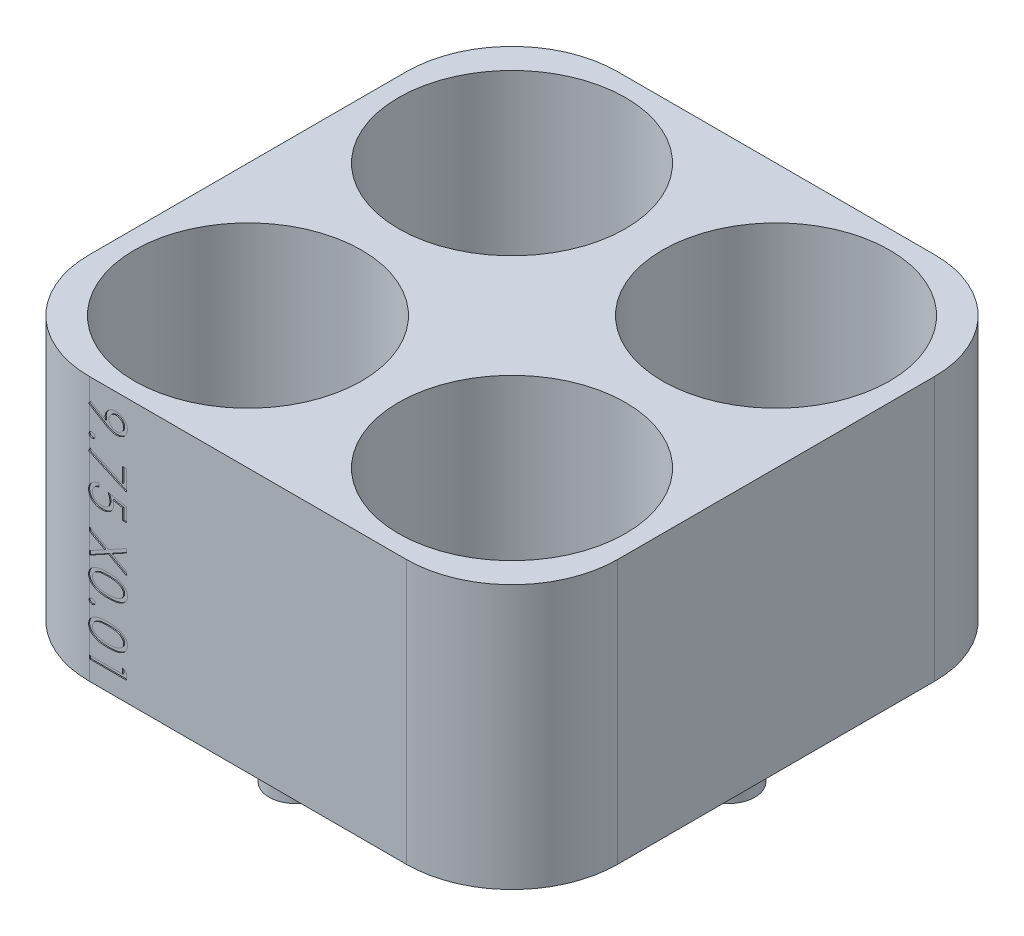
SolidWorks part; units mm, degrees
ref_plane "Alzado" through (0, 0, 0) normal (0, 0, 1) x (1, 0, 0)
ref_plane "Planta" through (0, 0, 0) normal (0, 1, 0) x (1, 0, 0)
ref_plane "Vista lateral" through (0, 0, 0) normal (1, 0, 0) x (0, 0, -1)
sketch "Croquis1" plane through (0, 0, 0) normal (0, 1, 0) x (1, 0, 0)
  line L1 (-25, 25) -> (25, 25)
  line L2 (-25, 25) -> (-25, -25)
  line L3 (-25, -25) -> (25, -25)
  line L4 (25, 25) -> (25, -25)
  line L5 (-25, 25) -> (25, -25) construction
  line L6 (-25, -25) -> (25, 25) construction
  point P0 (0, 0)
  dimension "D1" = 50
  dimension "D2" = 50
extrude "Saliente-Extruir1" add sketch "Croquis1" along normal blind 25
sketch "Croquis2" plane through (0, 25, 0) normal (0, 1, 0) x (1, 0, 0)
  line L1 (-25, 25) -> (-25, -25) construction
  line L2 (25, 25) -> (-25, 25) construction
  circle A0 centre (-12.5, 12.5) radius 10.75
  dimension "D1" = 21.5
  dimension "D2" = 12.5
  dimension "D3" = 12.5
extrude "Cortar-Extruir1" cut sketch "Croquis2" against normal blind 34
pattern_linear "MatrizL1" count 2 spacing 25 along (1, 0, 0) count 2 spacing 25 along (0, 0, 1) of "Cortar-Extruir1"
sketch "Croquis3" plane through (0, 0, 0) normal (0, -1, 0) x (1, 0, 0)
  line L0 (0, 7.2028) -> (0, 11.424) construction
  line L1 (-2.5, 0) -> (-5.3602, 0) construction
  circle A0 centre (0, 0) radius 2.5
  circle A1 centre (20.5, 0) radius 2.5
  circle A2 centre (-20.5, 0) radius 2.5
  circle A3 centre (0, 20.5) radius 2.5
  circle A4 centre (0, -20.5) radius 2.5
  dimension "D1" = 5
  dimension "D2" = 5
  dimension "D5" = 5
  dimension "D3" = 20.5
  dimension "D4" = 20.5
extrude "Saliente-Extruir2" add sketch "Croquis3" along normal blind 3
fillet "Redondeo3" radius 10 4 edges at (-25, 12.5, -25) (25, 12.5, -25) (25, 12.5, 25) (-25, 12.5, 25)
sketch "Croquis6" plane through (25, 0, 0) normal (1, 0, 0) x (0, 0, -1)
  line L5 (-15, 25) -> (15, 25) construction
  line L6 (-1.0144, 25) -> (5.0005, 25)
  line L7 (-1.0144, 25) -> (-1.0144, 23.8299)
  line L8 (-1.0144, 23.8299) -> (5.0005, 23.8299)
  line L9 (5.0005, 25) -> (5.0005, 23.8299)
sketch "Croquis7" plane through (0, 0, -25) normal (0, 0, -1) x (-1, 0, 0)
  line L0 (7.8632, 14.1683) -> (8.4844, 13.6947)
  line L1 (8.4844, 13.6947) -> (9.1494, 13.7051)
  line L2 (10.3053, 7.9462) -> (10.3053, 7.1749)
  line L3 (10.3053, 7.1749) -> (10.031, 7.1749)
  line L4 (10.031, 7.1749) -> (9.7567, 7.1749)
  line L5 (9.7567, 7.1749) -> (9.7567, 7.9064)
  line L6 (8.8152, 8.9851) -> (8.2479, 8.958)
  line L7 (8.2479, 8.958) -> (8.2217, 8.0664)
  line L8 (8.2217, 8.0664) -> (8.1956, 7.1749)
  line L9 (8.1956, 7.1749) -> (7.9246, 7.1749)
  line L10 (7.9246, 7.1749) -> (7.6536, 7.1749)
  line L11 (7.6536, 7.1749) -> (7.6536, 8.2734)
  line L12 (7.6536, 8.2734) -> (7.6536, 9.372)
  line L13 (7.6536, 9.372) -> (7.3564, 9.6424)
  line L14 (-2.7058, 14.0872) -> (-2.3467, 13.6793)
  line L15 (-2.3467, 13.6793) -> (-1.6645, 14.3361)
  line L16 (-1.6495, 11.3447) -> (-2.312, 11.9941)
  line L17 (-2.312, 11.9941) -> (-2.981, 11.3447)
  line L18 (-9.4499, 8.7294) -> (-8.8056, 8.7294)
  line L19 (-8.8056, 8.7294) -> (-8.8056, 8.455)
  line L20 (-8.8056, 8.455) -> (-8.8056, 8.1807)
  line L21 (-8.8056, 8.1807) -> (-9.4064, 8.1807)
  line L22 (-9.2629, 7.7692) -> (-8.577, 7.7692)
  line L23 (-8.577, 7.7692) -> (-8.577, 8.3636)
  line L24 (-8.577, 8.3636) -> (-8.577, 8.958)
  line L25 (-8.577, 8.958) -> (-9.2857, 8.9847)
  line L26 (-9.2857, 8.9847) -> (-9.9944, 9.0114)
  line L27 (-9.9944, 9.0114) -> (-9.9944, 9.2818)
  line L28 (-9.9944, 9.2818) -> (-9.9944, 9.5523)
  line L29 (-9.9944, 9.5523) -> (-9.304, 9.5523)
  line L30 (-5.4224, 9.2818) -> (-5.4224, 9.0114)
  line L31 (-5.4224, 9.0114) -> (-6.131, 8.9847)
  line L32 (-6.131, 8.9847) -> (-6.8397, 8.958)
  line L33 (-6.8397, 8.958) -> (-6.8659, 8.0664)
  line L34 (-6.8659, 8.0664) -> (-6.892, 7.1749)
  line L35 (-6.892, 7.1749) -> (-7.163, 7.1749)
  line L36 (-7.163, 7.1749) -> (-7.434, 7.1749)
  line L37 (-7.434, 7.1749) -> (-7.434, 8.1741)
  line L38 (-6.1873, 9.5523) -> (-5.4224, 9.5523)
  line L39 (-5.4224, 9.5523) -> (-5.4224, 9.2818)
  line L40 (-2.9535, 9.278) -> (-2.9535, 9.0037)
  line L41 (-2.9535, 9.0037) -> (-3.621, 9.0037)
  line L42 (-4.508, 7.9796) -> (-4.508, 7.1749)
  line L43 (-4.508, 7.1749) -> (-4.7906, 7.1749)
  line L44 (-4.7906, 7.1749) -> (-5.0732, 7.1749)
  line L45 (-5.0732, 7.1749) -> (-5.0421, 8.1431)
  line L46 (-3.7256, 9.5523) -> (-2.9535, 9.5523)
  line L47 (-2.9535, 9.5523) -> (-2.9535, 9.278)
  line L48 (-1.1662, 7.9978) -> (-1.8562, 7.9978)
  line L49 (-1.8562, 7.9978) -> (-1.8562, 8.2722)
  line L50 (-1.8562, 8.2722) -> (-1.8562, 8.5465)
  line L51 (-1.8562, 8.5465) -> (-1.2098, 8.5465)
  line L52 (-1.3075, 8.958) -> (-1.9934, 8.958)
  line L53 (-1.9934, 8.958) -> (-1.9934, 8.3636)
  line L54 (-1.9934, 8.3636) -> (-1.9934, 7.7692)
  line L55 (-1.9934, 7.7692) -> (-1.3761, 7.7422)
  line L56 (-1.3761, 7.7422) -> (-0.7589, 7.7152)
  line L57 (-0.7589, 7.7152) -> (-0.7589, 7.4353)
  line L58 (-0.7589, 7.4353) -> (-0.7589, 7.1555)
  line L59 (-0.7589, 7.1555) -> (-1.4994, 7.1891)
  line L60 (2.4415, 9.2818) -> (2.4415, 9.0114)
  line L61 (2.4415, 9.0114) -> (1.7328, 8.9847)
  line L62 (1.7328, 8.9847) -> (1.0242, 8.958)
  line L63 (1.0242, 8.958) -> (0.998, 8.0664)
  line L64 (0.998, 8.0664) -> (0.9718, 7.1749)
  line L65 (0.9718, 7.1749) -> (0.7008, 7.1749)
  line L66 (0.7008, 7.1749) -> (0.4298, 7.1749)
  line L67 (0.4298, 7.1749) -> (0.4298, 8.1741)
  line L68 (1.6766, 9.5523) -> (2.4415, 9.5523)
  line L69 (2.4415, 9.5523) -> (2.4415, 9.2818)
  line L70 (3.6718, 8.7294) -> (4.3617, 8.7294)
  line L71 (4.3617, 8.7294) -> (4.3617, 8.455)
  line L72 (4.3617, 8.455) -> (4.3617, 8.1807)
  line L73 (4.3617, 8.1807) -> (3.7153, 8.1807)
  line L74 (3.7641, 9.0037) -> (3.0816, 9.0037)
  line L75 (3.0816, 9.0037) -> (3.0816, 9.278)
  line L76 (3.0816, 9.278) -> (3.0816, 9.5523)
  line L77 (3.0816, 9.5523) -> (3.863, 9.5523)
  line L78 (7.1049, 8.3636) -> (7.1049, 7.1749)
  line L79 (7.1049, 7.1749) -> (6.8306, 7.1749)
  line L80 (6.8306, 7.1749) -> (6.5563, 7.1749)
  line L81 (6.5563, 7.1749) -> (6.5563, 8.3636)
  line L82 (6.5563, 8.3636) -> (6.5563, 9.5523)
  line L83 (6.5563, 9.5523) -> (6.8306, 9.5523)
  line L84 (6.8306, 9.5523) -> (7.1049, 9.5523)
  line L85 (7.1049, 9.5523) -> (7.1049, 8.3636)
  line L86 (0.8827, 14.6336) -> (0.7629, 14.6662)
  line L87 (-13.4691, 8.7327) -> (-13.4691, 7.7235)
  line L88 (-13.4691, 7.7235) -> (-12.4632, 7.7235)
  line L89 (-12.4632, 7.7235) -> (-11.4574, 7.7235)
  line L90 (-11.4574, 7.7235) -> (-11.4574, 7.9795)
  line L91 (-12.4358, 8.455) -> (-13.1948, 8.455)
  line L92 (-13.1948, 8.455) -> (-13.1948, 8.719)
  line L93 (-12.5776, 9.7156) -> (-13.4691, 9.7418)
  line L94 (-13.4691, 9.7418) -> (-13.4691, 8.7327)
  arc A0 (7.8207, 15.7172) -> (7.8364, 15.7705) centre (7.7385, 15.7705) ccw
  arc A1 (7.7403, 15.5996) -> (7.8207, 15.7172) centre (5.4553, 17.249) ccw
  arc A2 (7.6344, 15.4624) -> (7.7403, 15.5996) centre (5.511, 17.2088) ccw
  arc A3 (7.509, 15.3169) -> (7.6344, 15.4624) centre (4.4381, 18.0912) ccw
  arc A4 (7.509, 15.3169) -> (7.3859, 15.1667) centre (9.0083, 13.9623) ccw
  arc A5 (7.3859, 15.1667) -> (7.2866, 15.015) centre (8.617, 14.2528) ccw
  arc A6 (7.2866, 15.015) -> (7.2205, 14.8813) centre (8.3511, 14.4051) ccw
  arc A7 (7.2205, 14.8813) -> (7.2118, 14.7982) centre (7.3529, 14.8255) ccw
  arc A8 (7.2118, 14.7982) -> (7.2549, 14.7131) centre (7.3828, 14.8313) ccw
  arc A9 (7.2549, 14.7131) -> (7.4157, 14.5487) centre (10.2671, 17.4976) ccw
  arc A10 (7.4157, 14.5487) -> (7.6231, 14.3611) centre (10.3207, 17.5531) ccw
  arc A11 (7.6231, 14.3611) -> (7.8632, 14.1683) centre (11.5806, 19.0439) ccw
  arc A12 (9.1494, 13.7051) -> (9.6224, 13.7371) centre (9.0782, 18.267) ccw
  arc A13 (9.6224, 13.7371) -> (9.942, 13.8238) centre (9.4861, 14.8713) ccw
  arc A14 (9.942, 13.8238) -> (10.2456, 14.0053) centre (9.39, 15.0921) ccw
  arc A15 (10.2456, 14.0053) -> (10.6786, 14.3706) centre (5.0774, 20.5705) ccw
  arc A16 (10.6786, 14.3706) -> (10.8157, 14.5072) centre (9.344, 15.8478) ccw
  arc A17 (10.8157, 14.5072) -> (10.9316, 14.6498) centre (9.6175, 15.5987) ccw
  arc A18 (10.9316, 14.6498) -> (11.0142, 14.7795) centre (9.864, 15.4207) ccw
  arc A19 (11.0142, 14.7795) -> (11.0368, 14.8667) centre (10.8577, 14.8667) ccw
  arc A20 (11.0368, 14.8667) -> (11.0138, 14.9543) centre (10.8588, 14.8667) ccw
  arc A21 (11.0138, 14.9543) -> (10.9294, 15.0856) centre (9.8293, 14.2855) ccw
  arc A22 (10.9294, 15.0856) -> (10.8111, 15.2305) centre (9.5779, 14.1027) ccw
  arc A23 (10.8111, 15.2305) -> (10.6711, 15.3696) centre (9.282, 13.8321) ccw
  arc A24 (10.531, 15.5023) -> (10.6711, 15.3696) centre (13.4494, 18.4448) ccw
  arc A25 (10.4128, 15.6274) -> (10.531, 15.5023) centre (12.3843, 17.371) ccw
  arc A26 (10.3221, 15.7353) -> (10.4128, 15.6274) centre (12.5085, 17.4808) ccw
  arc A27 (10.3053, 15.7832) -> (10.3221, 15.7353) centre (10.3821, 15.7832) ccw
  arc A28 (10.3608, 15.8219) -> (10.3053, 15.7832) centre (10.3466, 15.7832) ccw
  arc A29 (10.5656, 15.7289) -> (10.3608, 15.8219) centre (9.8279, 14.3762) ccw
  arc A30 (10.8002, 15.5792) -> (10.5656, 15.7289) centre (9.599, 13.9564) ccw
  arc A31 (10.9826, 15.4138) -> (10.8002, 15.5792) centre (10.0591, 14.578) ccw
  arc A32 (10.9826, 15.4138) -> (11.0637, 15.3403) centre (11.3967, 15.7885) ccw
  arc A33 (11.0637, 15.3403) -> (11.1631, 15.2781) centre (11.5017, 15.9299) ccw
  arc A34 (11.1631, 15.2781) -> (11.265, 15.2354) centre (11.4705, 15.8698) ccw
  arc A35 (11.265, 15.2354) -> (11.3528, 15.2216) centre (11.3528, 15.5063) ccw
  arc A36 (11.5105, 15.1947) -> (11.3528, 15.2216) centre (11.3528, 14.7446) ccw
  arc A37 (11.6455, 15.1174) -> (11.5105, 15.1947) centre (11.3692, 14.7916) ccw
  arc A38 (11.7362, 15.0028) -> (11.6455, 15.1174) centre (11.405, 14.8338) ccw
  arc A39 (11.7684, 14.8692) -> (11.7362, 15.0028) centre (11.4744, 14.8692) ccw
  arc A40 (11.7684, 14.8692) -> (11.79, 14.7971) centre (11.8993, 14.8692) ccw
  arc A41 (11.79, 14.7971) -> (11.8825, 14.6685) centre (13.4278, 15.8772) ccw
  arc A42 (11.8825, 14.6685) -> (12.0082, 14.5215) centre (13.633, 16.0377) ccw
  arc A43 (12.0082, 14.5215) -> (12.157, 14.3724) centre (14.2933, 16.654) ccw
  arc A44 (12.438, 14.0823) -> (12.157, 14.3724) centre (9.3325, 11.356) ccw
  arc A45 (12.4278, 13.9645) -> (12.438, 14.0823) centre (12.3765, 14.0283) ccw
  arc A46 (12.2881, 13.9582) -> (12.4278, 13.9645) centre (12.3537, 14.0566) ccw
  arc A47 (11.9498, 14.2059) -> (12.2881, 13.9582) centre (14.8744, 17.8451) ccw
  arc A48 (11.9498, 14.2059) -> (11.8015, 14.3147) centre (10.6506, 12.5892) ccw
  arc A49 (11.8015, 14.3147) -> (11.6481, 14.4066) centre (10.7739, 12.7741) ccw
  arc A50 (11.6481, 14.4066) -> (11.5101, 14.4719) centre (10.9149, 13.0372) ccw
  arc A51 (11.5101, 14.4719) -> (11.4191, 14.4901) centre (11.4191, 14.2524) ccw
  arc A52 (11.4191, 14.4901) -> (11.2737, 14.4365) centre (11.4191, 14.2662) ccw
  arc A53 (11.2737, 14.4365) -> (11.0199, 14.2002) centre (13.8839, 11.378) ccw
  arc A54 (11.0199, 14.2002) -> (10.703, 13.8512) centre (15.1341, 10.1459) ccw
  arc A55 (10.703, 13.8512) -> (10.3171, 13.3718) centre (23.3414, 3.2831) ccw
  arc A56 (10.3171, 13.3718) -> (10.2657, 13.2677) centre (10.5478, 13.1931) ccw
  arc A57 (10.2657, 13.2677) -> (10.2276, 13.0849) centre (11.9738, 12.816) ccw
  arc A58 (10.2276, 13.0849) -> (10.2027, 12.8512) centre (12.7023, 12.7038) ccw
  arc A59 (10.2027, 12.8512) -> (10.1946, 12.5765) centre (14.86, 12.5765) ccw
  arc A60 (10.1946, 12.5765) -> (10.204, 12.2376) centre (16.3162, 12.5765) ccw
  arc A61 (10.204, 12.2376) -> (10.2357, 12.0059) centre (11.6523, 12.3179) ccw
  arc A62 (10.2357, 12.0059) -> (10.2978, 11.8205) centre (11.1359, 12.2042) ccw
  arc A63 (10.2978, 11.8205) -> (10.4015, 11.6373) centre (11.4166, 12.3327) ccw
  arc A64 (10.4015, 11.6373) -> (10.6632, 11.2924) centre (14.0932, 14.1663) ccw
  arc A65 (10.6632, 11.2924) -> (10.9626, 10.9662) centre (14.4096, 14.4314) ccw
  arc A66 (10.9626, 10.9662) -> (11.2451, 10.7049) centre (14.694, 14.7173) ccw
  arc A67 (11.2451, 10.7049) -> (11.3944, 10.6496) centre (11.3944, 10.8787) ccw
  arc A68 (11.3944, 10.6496) -> (11.4678, 10.669) centre (11.3944, 10.7979) ccw
  arc A69 (11.4678, 10.669) -> (11.591, 10.7467) centre (10.6583, 12.0903) ccw
  arc A70 (11.591, 10.7467) -> (11.7308, 10.8535) centre (10.4984, 12.3206) ccw
  arc A71 (11.7308, 10.8535) -> (11.8705, 10.98) centre (10.1105, 12.7824) ccw
  arc A72 (12.1865, 11.2633) -> (11.8705, 10.98) centre (15.333, 7.434) ccw
  arc A73 (12.3254, 11.2717) -> (12.1865, 11.2633) centre (12.2618, 11.1718) ccw
  arc A74 (12.3462, 11.1583) -> (12.3254, 11.2717) centre (12.2831, 11.2053) ccw
  arc A75 (12.0866, 10.8425) -> (12.3462, 11.1583) centre (8.8334, 13.7815) ccw
  arc A76 (12.0866, 10.8425) -> (11.9503, 10.6793) centre (14.1042, 9.0197) ccw
  arc A77 (11.9503, 10.6793) -> (11.8331, 10.5124) centre (13.7779, 9.2711) ccw
  arc A78 (11.8331, 10.5124) -> (11.7469, 10.3632) centre (13.4831, 9.4593) ccw
  arc A79 (11.7469, 10.3632) -> (11.7198, 10.2678) centre (11.9646, 10.2498) ccw
  arc A80 (11.6821, 10.1339) -> (11.7198, 10.2678) centre (11.3722, 10.2934) ccw
  arc A81 (11.5944, 10.0217) -> (11.6821, 10.1339) centre (11.3432, 10.3083) ccw
  arc A82 (11.4687, 9.9467) -> (11.5944, 10.0217) centre (11.3273, 10.3265) ccw
  arc A83 (11.3222, 9.9195) -> (11.4687, 9.9467) centre (11.3174, 10.353) ccw
  arc A84 (11.3222, 9.9195) -> (11.2525, 9.9004) centre (11.3238, 9.7769) ccw
  arc A85 (11.2525, 9.9004) -> (11.124, 9.8199) centre (12.3164, 8.0596) ccw
  arc A86 (11.124, 9.8199) -> (10.9761, 9.711) centre (12.4479, 7.8656) ccw
  arc A87 (10.9761, 9.711) -> (10.8246, 9.5823) centre (12.9922, 7.183) ccw
  arc A88 (10.5215, 9.3355) -> (10.8246, 9.5823) centre (8.2644, 12.4162) ccw
  arc A89 (10.4143, 9.3612) -> (10.5215, 9.3355) centre (10.4788, 9.3938) ccw
  arc A90 (10.43, 9.5064) -> (10.4143, 9.3612) centre (10.534, 9.4217) ccw
  arc A91 (10.7064, 9.816) -> (10.43, 9.5064) centre (14.0228, 6.5776) ccw
  arc A92 (10.7064, 9.816) -> (10.8329, 9.9529) centre (8.2825, 12.1828) ccw
  arc A93 (10.8329, 9.9529) -> (10.9398, 10.0845) centre (9.0895, 11.4772) ccw
  arc A94 (10.9398, 10.0845) -> (11.0198, 10.1981) centre (9.1777, 11.4109) ccw
  arc A95 (11.0198, 10.1981) -> (11.0368, 10.255) centre (10.9335, 10.255) ccw
  arc A96 (11.0368, 10.255) -> (10.9841, 10.3809) centre (10.86, 10.255) ccw
  arc A97 (10.9841, 10.3809) -> (10.491, 10.8589) centre (-17.2866, -18.295) ccw
  arc A98 (10.491, 10.8589) -> (9.9956, 11.3213) centre (-12.443, -13.2114) ccw
  arc A99 (9.9956, 11.3213) -> (9.8429, 11.3925) centre (9.806, 11.1141) ccw
  arc A100 (9.8429, 11.3925) -> (9.4672, 11.4208) centre (9.4061, 8.0975) ccw
  arc A101 (9.4672, 11.4208) -> (8.9452, 11.4189) centre (9.2489, -0.4536) ccw
  arc A102 (8.9452, 11.4189) -> (8.4316, 11.3984) centre (9.4014, -6.4151) ccw
  arc A103 (8.4316, 11.3984) -> (8.2536, 11.3519) centre (8.4566, 10.9386) ccw
  arc A104 (8.2536, 11.3519) -> (7.9869, 11.175) centre (8.8016, 10.2362) ccw
  arc A105 (7.9869, 11.175) -> (7.6125, 10.8268) centre (12.8611, 5.5589) ccw
  arc A106 (7.6125, 10.8268) -> (7.2577, 10.4565) centre (15.4297, 2.9809) ccw
  arc A107 (7.2577, 10.4565) -> (7.1964, 10.2985) centre (7.4305, 10.2985) ccw
  arc A108 (7.1964, 10.2985) -> (7.2145, 10.2244) centre (7.3572, 10.2985) ccw
  arc A109 (7.2145, 10.2244) -> (7.2822, 10.1089) centre (8.3772, 10.8285) ccw
  arc A110 (7.2822, 10.1089) -> (7.3767, 9.9798) centre (8.6008, 10.9755) ccw
  arc A111 (7.3767, 9.9798) -> (7.4886, 9.8538) centre (8.8808, 11.2032) ccw
  arc A112 (7.4886, 9.8538) -> (7.6904, 9.6721) centre (8.9275, 11.2485) ccw
  arc A113 (7.6904, 9.6721) -> (7.8549, 9.5907) centre (7.9674, 10.025) ccw
  arc A114 (7.8549, 9.5907) -> (8.0864, 9.5585) centre (8.1095, 10.5738) ccw
  arc A115 (8.0864, 9.5585) -> (8.6545, 9.552) centre (8.6644, 35.0044) ccw
  arc A116 (9.1215, 9.544) -> (8.6545, 9.552) centre (8.649, -4.5201) ccw
  arc A117 (9.4164, 9.5162) -> (9.1215, 9.544) centre (9.0393, 7.0978) ccw
  arc A118 (9.6332, 9.4615) -> (9.4164, 9.5162) centre (9.2303, 8.3229) ccw
  arc A119 (9.8275, 9.3691) -> (9.6332, 9.4615) centre (9.2866, 8.4818) ccw
  arc A120 (10.07, 9.1656) -> (9.8275, 9.3691) centre (9.2785, 8.4685) ccw
  arc A121 (10.2136, 8.9165) -> (10.07, 9.1656) centre (9.5244, 8.685) ccw
  arc A122 (10.2855, 8.5518) -> (10.2136, 8.9165) centre (8.8473, 8.4577) ccw
  arc A123 (10.3053, 7.9462) -> (10.2855, 8.5518) centre (1.0313, 7.9462) ccw
  arc A124 (9.7567, 7.9064) -> (9.7228, 8.5244) centre (4.1088, 7.9064) ccw
  arc A125 (9.7228, 8.5244) -> (9.5911, 8.8245) centre (9.1787, 8.4645) ccw
  arc A126 (9.5911, 8.8245) -> (9.3262, 8.9654) centre (9.2738, 8.5476) ccw
  arc A127 (9.3262, 8.9654) -> (8.8152, 8.9851) centre (8.9569, 6.0198) ccw
  arc A128 (7.3564, 9.6424) -> (7.2288, 9.746) centre (6.3626, 8.55) ccw
  arc A129 (7.2288, 9.746) -> (7.0914, 9.8341) centre (6.3868, 8.5834) ccw
  arc A130 (7.0914, 9.8341) -> (6.9639, 9.8963) centre (6.5037, 8.7908) ccw
  arc A131 (6.9639, 9.8963) -> (6.8717, 9.9154) centre (6.8682, 9.6665) ccw
  arc A132 (6.7131, 9.9457) -> (6.8717, 9.9154) centre (6.8784, 10.381) ccw
  arc A133 (6.5817, 10.028) -> (6.7131, 9.9457) centre (6.8541, 10.3171) ccw
  arc A134 (6.4953, 10.1513) -> (6.5817, 10.028) centre (6.8364, 10.2983) ccw
  arc A135 (6.4648, 10.2988) -> (6.4953, 10.1513) centre (6.8376, 10.2988) ccw
  arc A136 (6.4648, 10.2988) -> (6.4415, 10.3832) centre (6.3005, 10.2988) ccw
  arc A137 (6.4415, 10.3832) -> (6.3508, 10.5191) centre (5.0271, 9.5374) ccw
  arc A138 (6.3508, 10.5191) -> (6.2253, 10.6717) centre (4.7662, 9.3438) ccw
  arc A139 (6.2253, 10.6717) -> (6.0768, 10.8221) centre (4.3143, 8.9327) ccw
  arc A140 (5.9325, 10.9654) -> (6.0768, 10.8221) centre (8.2667, 13.1698) ccw
  arc A141 (5.8213, 11.0963) -> (5.9325, 10.9654) centre (7.1292, 12.0955) ccw
  arc A142 (5.7469, 11.2041) -> (5.8213, 11.0963) centre (6.8945, 11.9163) ccw
  arc A143 (5.7519, 11.2473) -> (5.7469, 11.2041) centre (5.7767, 11.2225) ccw
  arc A144 (5.8578, 11.2647) -> (5.7519, 11.2473) centre (5.8169, 11.1823) ccw
  arc A145 (6.131, 11.1127) -> (5.8578, 11.2647) centre (4.3782, 8.2823) ccw
  arc A146 (6.3917, 10.9301) -> (6.131, 11.1127) centre (4.6509, 8.7227) ccw
  arc A147 (6.4986, 10.7849) -> (6.3917, 10.9301) centre (6.1812, 10.6631) ccw
  arc A148 (6.4986, 10.7849) -> (6.6024, 10.6772) centre (6.6776, 10.8536) ccw
  arc A149 (6.6024, 10.6772) -> (6.7608, 10.6678) centre (6.6948, 10.8938) ccw
  arc A150 (6.7608, 10.6678) -> (6.9698, 10.7749) centre (6.5856, 11.2676) ccw
  arc A151 (6.9698, 10.7749) -> (7.2092, 10.9925) centre (5.6507, 12.4663) ccw
  arc A152 (7.2092, 10.9925) -> (7.6024, 11.44) centre (1.2864, 16.5932) ccw
  arc A153 (7.6024, 11.44) -> (7.8101, 11.7698) centre (6.3648, 12.4497) ccw
  arc A154 (7.8101, 11.7698) -> (7.9156, 12.1133) centre (6.658, 12.3118) ccw
  arc A155 (7.9156, 12.1133) -> (7.9614, 12.5915) centre (4.0276, 12.7269) ccw
  arc A156 (7.9614, 12.5915) -> (7.9658, 12.9697) centre (-0.2685, 12.8749) ccw
  arc A157 (7.9658, 12.9697) -> (7.9414, 13.1961) centre (6.7728, 12.9559) ccw
  arc A158 (7.9414, 13.1961) -> (7.8789, 13.3759) centre (7.2334, 13.0506) ccw
  arc A159 (7.8789, 13.3759) -> (7.7592, 13.5757) centre (6.4557, 12.6586) ccw
  arc A160 (7.7592, 13.5757) -> (7.479, 13.9431) centre (2.8327, 10.1098) ccw
  arc A161 (7.479, 13.9431) -> (7.2074, 14.235) centre (4.8934, 11.8099) ccw
  arc A162 (7.2074, 14.235) -> (6.9674, 14.4357) centre (5.5572, 12.5055) ccw
  arc A163 (6.9674, 14.4357) -> (6.8009, 14.4901) centre (6.8009, 14.2078) ccw
  arc A164 (6.8009, 14.4901) -> (6.7093, 14.4691) centre (6.8009, 14.2792) ccw
  arc A165 (6.7093, 14.4691) -> (6.5669, 14.3915) centre (7.4157, 13.0051) ccw
  arc A166 (6.5669, 14.3915) -> (6.4078, 14.2829) centre (7.5845, 12.7294) ccw
  arc A167 (6.4078, 14.2829) -> (6.2526, 14.1543) centre (7.8163, 12.4235) ccw
  arc A168 (5.9495, 13.9075) -> (6.2526, 14.1543) centre (3.6924, 16.9882) ccw
  arc A169 (5.8423, 13.9332) -> (5.9495, 13.9075) centre (5.9068, 13.9658) ccw
  arc A170 (5.858, 14.0784) -> (5.8423, 13.9332) centre (5.962, 13.9937) ccw
  arc A171 (6.1344, 14.388) -> (5.858, 14.0784) centre (9.4508, 11.1496) ccw
  arc A172 (6.1344, 14.388) -> (6.2609, 14.5277) centre (4.3353, 16.1447) ccw
  arc A173 (6.2609, 14.5277) -> (6.3678, 14.6675) centre (4.7953, 15.7585) ccw
  arc A174 (6.3678, 14.6675) -> (6.4454, 14.7907) centre (5.0259, 15.5984) ccw
  arc A175 (6.4454, 14.7907) -> (6.4648, 14.8643) centre (6.3162, 14.8643) ccw
  arc A176 (6.4958, 14.9979) -> (6.4648, 14.8643) centre (6.7686, 14.8643) ccw
  arc A177 (6.5836, 15.1144) -> (6.4958, 14.9979) centre (6.8417, 14.8285) ccw
  arc A178 (6.7126, 15.1939) -> (6.5836, 15.1144) centre (6.8641, 14.8037) ccw
  arc A179 (6.8607, 15.2216) -> (6.7126, 15.1939) centre (6.8607, 14.8125) ccw
  arc A180 (6.8607, 15.2216) -> (6.9513, 15.2418) centre (6.8607, 15.4347) ccw
  arc A181 (6.9513, 15.2418) -> (7.0893, 15.3156) centre (6.3077, 16.6115) ccw
  arc A182 (7.0893, 15.3156) -> (7.2427, 15.4191) centre (6.1486, 16.8752) ccw
  arc A183 (7.2427, 15.4191) -> (7.3913, 15.5416) centre (5.9615, 17.1242) ccw
  arc A184 (7.6394, 15.7605) -> (7.3913, 15.5416) centre (16.6562, 5.2864) ccw
  arc A185 (7.7547, 15.8381) -> (7.6394, 15.7605) centre (8.0247, 15.3129) ccw
  arc A186 (7.8098, 15.8308) -> (7.7547, 15.8381) centre (7.777, 15.7948) ccw
  arc A187 (7.8364, 15.7705) -> (7.8098, 15.8308) centre (7.7548, 15.7705) ccw
  arc A188 (-4.1735, 15.2369) -> (-4.6255, 15.4401) centre (-5.4338, 13.0378) ccw
  arc A189 (-3.6355, 14.8943) -> (-4.1735, 15.2369) centre (-7.5658, 9.3178) ccw
  arc A190 (-3.1136, 14.4889) -> (-3.6355, 14.8943) centre (-7.7378, 9.0737) ccw
  arc A191 (-2.7058, 14.0872) -> (-3.1136, 14.4889) centre (-5.7294, 11.4256) ccw
  arc A192 (-1.0017, 14.9126) -> (-1.6645, 14.3361) centre (4.3593, 8.0795) ccw
  arc A193 (-0.4217, 15.2765) -> (-1.0017, 14.9126) centre (1.0153, 12.3417) ccw
  arc A194 (0.1537, 15.4744) -> (-0.4217, 15.2765) centre (0.6598, 13.0678) ccw
  arc A195 (0.7956, 15.5407) -> (0.1537, 15.4744) centre (0.7915, 12.4417) ccw
  arc A196 (1.1847, 15.5292) -> (0.7956, 15.5407) centre (0.7865, 8.6665) ccw
  arc A197 (1.4476, 15.4913) -> (1.1847, 15.5292) centre (1.0942, 13.9692) ccw
  arc A198 (1.6838, 15.4122) -> (1.4476, 15.4913) centre (1.151, 14.2139) ccw
  arc A199 (1.9772, 15.2664) -> (1.6838, 15.4122) centre (0.1274, 11.9118) ccw
  arc A200 (2.3788, 14.9896) -> (1.9772, 15.2664) centre (0.7926, 13.1182) ccw
  arc A201 (2.763, 14.6116) -> (2.3788, 14.9896) centre (0.0248, 12.2123) ccw
  arc A202 (3.0797, 14.1901) -> (2.763, 14.6116) centre (0.1218, 12.2973) ccw
  arc A203 (3.2772, 13.7827) -> (3.0797, 14.1901) centre (1.4583, 13.1525) ccw
  arc A204 (3.3233, 13.6068) -> (3.2772, 13.7827) centre (2.1631, 13.3967) ccw
  arc A205 (3.3622, 13.3516) -> (3.3233, 13.6068) centre (-1.2114, 12.7856) ccw
  arc A206 (3.3893, 13.0687) -> (3.3622, 13.3516) centre (-1.7499, 12.7189) ccw
  arc A207 (3.399, 12.7984) -> (3.3893, 13.0687) centre (-0.8303, 12.7815) ccw
  arc A208 (3.3017, 12.0425) -> (3.399, 12.7984) centre (0.506, 12.7868) ccw
  arc A209 (3.0106, 11.3734) -> (3.3017, 12.0425) centre (0.9449, 12.67) ccw
  arc A210 (2.5277, 10.8085) -> (3.0106, 11.3734) centre (0.8575, 12.7249) ccw
  arc A211 (1.8674, 10.3584) -> (2.5277, 10.8085) centre (0.3078, 13.3556) ccw
  arc A212 (1.6445, 10.2614) -> (1.8674, 10.3584) centre (1.0576, 11.9146) ccw
  arc A213 (1.4171, 10.1997) -> (1.6445, 10.2614) centre (1.1262, 11.7213) ccw
  arc A214 (1.1489, 10.1657) -> (1.4171, 10.1997) centre (1.0129, 12.3142) ccw
  arc A215 (0.7956, 10.1535) -> (1.1489, 10.1657) centre (0.7595, 16.3192) ccw
  arc A216 (0.1493, 10.217) -> (0.7956, 10.1535) centre (0.7772, 13.2854) ccw
  arc A217 (-0.427, 10.4128) -> (0.1493, 10.217) centre (0.6358, 12.5941) ccw
  arc A218 (-1.0017, 10.7741) -> (-0.427, 10.4128) centre (0.9552, 13.2498) ccw
  arc A219 (-1.6495, 11.3447) -> (-1.0017, 10.7741) centre (4.0247, 17.1332) ccw
  arc A220 (-3.6326, 10.7749) -> (-2.981, 11.3447) centre (-8.7936, 17.3333) ccw
  arc A221 (-4.2072, 10.414) -> (-3.6326, 10.7749) centre (-5.6168, 13.2963) ccw
  arc A222 (-4.7806, 10.2172) -> (-4.2072, 10.414) centre (-5.2824, 12.6125) ccw
  arc A223 (-5.4224, 10.1507) -> (-4.7806, 10.2172) centre (-5.4216, 13.2772) ccw
  arc A224 (-5.9428, 10.1875) -> (-5.4224, 10.1507) centre (-5.4215, 13.8704) ccw
  arc A225 (-6.3703, 10.299) -> (-5.9428, 10.1875) centre (-5.6718, 12.1016) ccw
  arc A226 (-6.7684, 10.507) -> (-6.3703, 10.299) centre (-5.6435, 12.1747) ccw
  arc A227 (-7.1992, 10.8393) -> (-6.7684, 10.507) centre (-4.3734, 14.0577) ccw
  arc A228 (-7.628, 11.3675) -> (-7.1992, 10.8393) centre (-5.8601, 12.3645) ccw
  arc A229 (-7.93, 12.0833) -> (-7.628, 11.3675) centre (-4.6606, 13.0409) ccw
  arc A230 (-8.0632, 12.8536) -> (-7.93, 12.0833) centre (-4.6226, 13.052) ccw
  arc A231 (-7.9916, 13.5443) -> (-8.0632, 12.8536) centre (-5.8998, 12.9784) ccw
  arc A232 (-7.7267, 14.1527) -> (-7.9916, 13.5443) centre (-5.7966, 12.9505) ccw
  arc A233 (-7.2696, 14.7396) -> (-7.7267, 14.1527) centre (-4.7051, 12.2706) ccw
  arc A234 (-6.7051, 15.2141) -> (-7.2696, 14.7396) centre (-4.7436, 12.3076) ccw
  arc A235 (-6.1205, 15.4878) -> (-6.7051, 15.2141) centre (-5.5415, 13.4899) ccw
  arc A236 (-5.767, 15.558) -> (-6.1205, 15.4878) centre (-5.537, 13.4743) ccw
  arc A237 (-5.3825, 15.573) -> (-5.767, 15.558) centre (-5.469, 12.8582) ccw
  arc A238 (-4.9932, 15.5333) -> (-5.3825, 15.573) centre (-5.4718, 12.7708) ccw
  arc A239 (-4.6255, 15.4401) -> (-4.9932, 15.5333) centre (-5.4167, 13.0887) ccw
  arc A240 (-11.1477, 9.8357) -> (-11.2454, 9.9892) centre (-12.2316, 9.2535) ccw
  arc A241 (-11.1073, 9.7094) -> (-11.1477, 9.8357) centre (-11.4682, 9.6636) ccw
  arc A242 (-11.1098, 9.5586) -> (-11.1073, 9.7094) centre (-11.6324, 9.6428) ccw
  arc A243 (-11.1588, 9.3072) -> (-11.1098, 9.5586) centre (-14.9842, 10.1826) ccw
  arc A244 (-11.1588, 9.3072) -> (-11.2075, 9.0588) centre (-7.2141, 8.4045) ccw
  arc A245 (-11.2075, 9.0588) -> (-11.211, 8.9103) centre (-10.6769, 8.9718) ccw
  arc A246 (-11.211, 8.9103) -> (-11.1734, 8.79) centre (-10.877, 8.9488) ccw
  arc A247 (-11.1734, 8.79) -> (-11.0833, 8.6523) centre (-10.3418, 9.2356) ccw
  arc A248 (-10.9464, 8.3681) -> (-11.0833, 8.6523) centre (-11.6578, 8.2004) ccw
  arc A249 (-10.9027, 7.9815) -> (-10.9464, 8.3681) centre (-12.542, 7.992) ccw
  arc A250 (-10.9507, 7.6059) -> (-10.9027, 7.9815) centre (-12.4755, 7.9916) ccw
  arc A251 (-11.0916, 7.3578) -> (-10.9507, 7.6059) centre (-11.4715, 7.7376) ccw
  arc A252 (-11.2431, 7.2577) -> (-11.0916, 7.3578) centre (-11.4122, 7.6783) ccw
  arc A253 (-11.4485, 7.2044) -> (-11.2431, 7.2577) centre (-11.5527, 8.028) ccw
  arc A254 (-11.7931, 7.1802) -> (-11.4485, 7.2044) centre (-11.8372, 10.2753) ccw
  arc A255 (-12.5364, 7.1749) -> (-11.7931, 7.1802) centre (-12.5364, 59.3435) ccw
  arc A256 (-13.1097, 7.1811) -> (-12.5364, 7.1749) centre (-12.5364, 33.73) ccw
  arc A257 (-13.5165, 7.2017) -> (-13.1097, 7.1811) centre (-12.9587, 14.1743) ccw
  arc A258 (-13.8053, 7.2334) -> (-13.5165, 7.2017) centre (-13.1246, 12.1001) ccw
  arc A259 (-13.908, 7.2846) -> (-13.8053, 7.2334) centre (-13.7802, 7.4124) ccw
  arc A260 (-13.9922, 7.4804) -> (-13.908, 7.2846) centre (-13.7044, 7.4882) ccw
  arc A261 (-14.0195, 8.7564) -> (-13.9922, 7.4804) centre (98.3572, 10.5257) ccw
  arc A262 (-14.0326, 10.035) -> (-14.0195, 8.7564) centre (101.8739, 10.5812) ccw
  arc A263 (-13.9543, 10.2253) -> (-14.0326, 10.035) centre (-13.7652, 10.0362) ccw
  arc A264 (-13.8976, 10.2502) -> (-13.9543, 10.2253) centre (-13.8941, 10.1651) ccw
  arc A265 (-13.5482, 10.2627) -> (-13.8976, 10.2502) centre (-12.7256, -17.6614) ccw
  arc A266 (-13.1369, 10.2686) -> (-13.5482, 10.2627) centre (-13.1495, -3.2714) ccw
  arc A267 (-12.661, 10.2634) -> (-13.1369, 10.2686) centre (-13.1594, -13.9436) ccw
  arc A268 (-11.8561, 10.2422) -> (-12.661, 10.2634) centre (-14.0796, -58.6346) ccw
  arc A269 (-11.5649, 10.2095) -> (-11.8561, 10.2422) centre (-11.9156, 8.3994) ccw
  arc A270 (-11.3946, 10.1359) -> (-11.5649, 10.2095) centre (-11.647, 9.7854) ccw
  arc A271 (-11.2454, 9.9892) -> (-11.3946, 10.1359) centre (-11.7962, 9.5783) ccw
  arc A272 (-8.1526, 9.2758) -> (-8.355, 9.4185) centre (-8.7713, 8.6134) ccw
  arc A273 (-8.0438, 9.1066) -> (-8.1526, 9.2758) centre (-8.4321, 8.9766) ccw
  arc A274 (-7.9944, 8.8403) -> (-8.0438, 9.1066) centre (-8.9671, 8.7975) ccw
  arc A275 (-7.9827, 8.3062) -> (-7.9944, 8.8403) centre (-20.1308, 8.3062) ccw
  arc A276 (-7.9903, 7.9145) -> (-7.9827, 8.3062) centre (-18.0236, 8.3062) ccw
  arc A277 (-8.0206, 7.7011) -> (-7.9903, 7.9145) centre (-9.0501, 7.9559) ccw
  arc A278 (-8.0862, 7.5491) -> (-8.0206, 7.7011) centre (-8.5095, 7.8221) ccw
  arc A279 (-8.2071, 7.3993) -> (-8.0862, 7.5491) centre (-8.8486, 8.0408) ccw
  arc A280 (-8.3641, 7.2752) -> (-8.2071, 7.3993) centre (-8.816, 8.0082) ccw
  arc A281 (-8.5268, 7.2101) -> (-8.3641, 7.2752) centre (-8.6335, 7.7122) ccw
  arc A282 (-8.7681, 7.1815) -> (-8.5268, 7.2101) centre (-8.8035, 8.5118) ccw
  arc A283 (-9.2628, 7.1749) -> (-8.7681, 7.1815) centre (-9.2628, 25.7665) ccw
  arc A284 (-9.7576, 7.1815) -> (-9.2628, 7.1749) centre (-9.2629, 25.7665) ccw
  arc A285 (-9.9989, 7.2101) -> (-9.7576, 7.1815) centre (-9.7222, 8.5118) ccw
  arc A286 (-10.1616, 7.2752) -> (-9.9989, 7.2101) centre (-9.8922, 7.7122) ccw
  arc A287 (-10.3186, 7.3993) -> (-10.1616, 7.2752) centre (-9.7097, 8.0082) ccw
  arc A288 (-10.4191, 7.5198) -> (-10.3186, 7.3993) centre (-9.7001, 8.0178) ccw
  arc A289 (-10.4889, 7.6488) -> (-10.4191, 7.5198) centre (-9.8701, 7.9001) ccw
  arc A290 (-10.5294, 7.7913) -> (-10.4889, 7.6488) centre (-9.8555, 7.906) ccw
  arc A291 (-10.543, 7.9521) -> (-10.5294, 7.7913) centre (-9.5843, 7.9521) ccw
  arc A292 (-10.5294, 8.1129) -> (-10.543, 7.9521) centre (-9.5843, 7.9521) ccw
  arc A293 (-10.4889, 8.2554) -> (-10.5294, 8.1129) centre (-9.8555, 7.9983) ccw
  arc A294 (-10.4191, 8.3844) -> (-10.4889, 8.2554) centre (-9.8701, 8.0042) ccw
  arc A295 (-10.3186, 8.5049) -> (-10.4191, 8.3844) centre (-9.7001, 7.8865) ccw
  arc A296 (-10.1709, 8.6247) -> (-10.3186, 8.5049) centre (-9.6697, 7.856) ccw
  arc A297 (-10.0216, 8.6906) -> (-10.1709, 8.6247) centre (-9.8954, 8.2022) ccw
  arc A298 (-9.8155, 8.7214) -> (-10.0216, 8.6906) centre (-9.7718, 7.7239) ccw
  arc A299 (-9.4499, 8.7294) -> (-9.8155, 8.7214) centre (-9.4499, 0.3704) ccw
  arc A300 (-9.4064, 8.1807) -> (-9.7821, 8.1762) centre (-9.4064, -7.6165) ccw
  arc A301 (-9.7821, 8.1762) -> (-9.9165, 8.1511) centre (-9.772, 7.7496) ccw
  arc A302 (-9.9165, 8.1511) -> (-9.9715, 8.0907) centre (-9.887, 8.069) ccw
  arc A303 (-9.9715, 8.0907) -> (-9.9779, 7.975) centre (-9.6832, 8.0168) ccw
  arc A304 (-9.9779, 7.975) -> (-9.9343, 7.861) centre (-9.7059, 8.0136) ccw
  arc A305 (-9.9343, 7.861) -> (-9.8507, 7.7999) centre (-9.809, 7.9447) ccw
  arc A306 (-9.8507, 7.7999) -> (-9.683, 7.7742) centre (-9.6672, 8.4377) ccw
  arc A307 (-9.683, 7.7742) -> (-9.2629, 7.7692) centre (-9.2629, 25.4122) ccw
  arc A308 (-9.0001, 9.5434) -> (-9.304, 9.5523) centre (-9.304, 4.3543) ccw
  arc A309 (-8.7294, 9.5165) -> (-9.0001, 9.5434) centre (-9.1953, 6.2114) ccw
  arc A310 (-8.5062, 9.4745) -> (-8.7294, 9.5165) centre (-9.0756, 7.0605) ccw
  arc A311 (-8.355, 9.4185) -> (-8.5062, 9.4745) centre (-8.6573, 8.8339) ccw
  arc A312 (-7.4288, 8.8108) -> (-7.434, 8.1741) centre (31.0839, 8.1741) ccw
  arc A313 (-7.4013, 9.0634) -> (-7.4288, 8.8108) centre (-6.0423, 8.7879) ccw
  arc A314 (-7.3325, 9.2188) -> (-7.4013, 9.0634) centre (-7.0143, 8.9849) ccw
  arc A315 (-7.1931, 9.3628) -> (-7.3325, 9.2188) centre (-6.7334, 8.7784) ccw
  arc A316 (-7.033, 9.46) -> (-7.1931, 9.3628) centre (-6.7135, 8.753) ccw
  arc A317 (-6.8534, 9.5166) -> (-7.033, 9.46) centre (-6.7067, 8.7381) ccw
  arc A318 (-6.6025, 9.5447) -> (-6.8534, 9.5166) centre (-6.5404, 7.8552) ccw
  arc A319 (-6.1873, 9.5523) -> (-6.6025, 9.5447) centre (-6.1873, -1.7463) ccw
  arc A320 (-3.621, 9.0037) -> (-3.8986, 8.9962) centre (-3.621, 3.8359) ccw
  arc A321 (-3.8986, 8.9962) -> (-4.1341, 8.9733) centre (-3.7516, 6.2642) ccw
  arc A322 (-4.1341, 8.9733) -> (-4.3166, 8.9393) centre (-3.8396, 6.8872) ccw
  arc A323 (-4.3166, 8.9393) -> (-4.3982, 8.8939) centre (-4.2782, 8.7739) ccw
  arc A324 (-4.3982, 8.8939) -> (-4.4455, 8.8061) centre (-4.2756, 8.7714) ccw
  arc A325 (-4.4455, 8.8061) -> (-4.4789, 8.6) centre (-1.9538, 8.2969) ccw
  arc A326 (-4.4789, 8.6) -> (-4.5009, 8.3248) centre (-0.998, 8.1823) ccw
  arc A327 (-4.5009, 8.3248) -> (-4.508, 7.9796) centre (3.9834, 7.9796) ccw
  arc A328 (-5.0166, 8.751) -> (-5.0421, 8.1431) centre (26.4441, 7.129) ccw
  arc A329 (-4.9794, 9.0068) -> (-5.0166, 8.751) centre (-3.6267, 8.6794) ccw
  arc A330 (-4.903, 9.1711) -> (-4.9794, 9.0068) centre (-4.5307, 8.8982) ccw
  arc A331 (-4.7543, 9.3318) -> (-4.903, 9.1711) centre (-4.1277, 8.6028) ccw
  arc A332 (-4.5833, 9.4508) -> (-4.7543, 9.3318) centre (-4.0867, 8.555) ccw
  arc A333 (-4.4113, 9.5153) -> (-4.5833, 9.4508) centre (-4.2803, 8.9043) ccw
  arc A334 (-4.1705, 9.5449) -> (-4.4113, 9.5153) centre (-4.1251, 8.1801) ccw
  arc A335 (-3.7256, 9.5523) -> (-4.1705, 9.5449) centre (-3.7256, -3.8112) ccw
  arc A336 (-0.1513, 9.2074) -> (-0.2518, 9.3279) centre (-0.8703, 8.7094) ccw
  arc A337 (-0.0815, 9.0784) -> (-0.1513, 9.2074) centre (-0.7003, 8.8271) ccw
  arc A338 (-0.041, 8.9359) -> (-0.0815, 9.0784) centre (-0.7149, 8.8212) ccw
  arc A339 (-0.0274, 8.7751) -> (-0.041, 8.9359) centre (-0.9861, 8.7751) ccw
  arc A340 (-0.041, 8.6143) -> (-0.0274, 8.7751) centre (-0.9861, 8.7751) ccw
  arc A341 (-0.0815, 8.4718) -> (-0.041, 8.6143) centre (-0.7149, 8.7289) ccw
  arc A342 (-0.1513, 8.3428) -> (-0.0815, 8.4718) centre (-0.7003, 8.723) ccw
  arc A343 (-0.2518, 8.2223) -> (-0.1513, 8.3428) centre (-0.8703, 8.8407) ccw
  arc A344 (-0.402, 8.1012) -> (-0.2518, 8.2223) centre (-0.8918, 8.8622) ccw
  arc A345 (-0.5545, 8.0356) -> (-0.402, 8.1012) centre (-0.6746, 8.5248) ccw
  arc A346 (-0.7694, 8.0054) -> (-0.5545, 8.0356) centre (-0.8104, 9.0778) ccw
  arc A347 (-1.1662, 7.9978) -> (-0.7694, 8.0054) centre (-1.1662, 18.3918) ccw
  arc A348 (-1.2098, 8.5465) -> (-0.802, 8.5508) centre (-1.2098, 27.8029) ccw
  arc A349 (-0.802, 8.5508) -> (-0.6589, 8.5756) centre (-0.8123, 9.0358) ccw
  arc A350 (-0.6589, 8.5756) -> (-0.6006, 8.6364) centre (-0.6875, 8.6614) ccw
  arc A351 (-0.6006, 8.6364) -> (-0.5925, 8.7522) centre (-0.8677, 8.7131) ccw
  arc A352 (-0.5925, 8.7522) -> (-0.6361, 8.8662) centre (-0.8645, 8.7136) ccw
  arc A353 (-0.6361, 8.8662) -> (-0.7197, 8.9273) centre (-0.7614, 8.7825) ccw
  arc A354 (-0.7197, 8.9273) -> (-0.8874, 8.953) centre (-0.9032, 8.2895) ccw
  arc A355 (-0.8874, 8.953) -> (-1.3075, 8.958) centre (-1.3075, -8.685) ccw
  arc A356 (-2.1182, 7.2557) -> (-1.4994, 7.1891) centre (-1.2708, 12.222) ccw
  arc A357 (-2.4111, 7.4154) -> (-2.1182, 7.2557) centre (-2.0317, 7.7628) ccw
  arc A358 (-2.5518, 7.7257) -> (-2.4111, 7.4154) centre (-2.0064, 7.786) ccw
  arc A359 (-2.5877, 8.3779) -> (-2.5518, 7.7257) centre (3.3484, 8.3779) ccw
  arc A360 (-2.5804, 8.7992) -> (-2.5877, 8.3779) centre (9.5929, 8.3779) ccw
  arc A361 (-2.5507, 9.0208) -> (-2.5804, 8.7992) centre (-1.4468, 8.76) ccw
  arc A362 (-2.4852, 9.1759) -> (-2.5507, 9.0208) centre (-2.0595, 8.9048) ccw
  arc A363 (-2.3633, 9.3279) -> (-2.4852, 9.1759) centre (-1.7309, 8.6955) ccw
  arc A364 (-2.2063, 9.4519) -> (-2.3633, 9.3279) centre (-1.7544, 8.719) ccw
  arc A365 (-2.0437, 9.5171) -> (-2.2063, 9.4519) centre (-1.9369, 9.0149) ccw
  arc A366 (-1.8023, 9.5457) -> (-2.0437, 9.5171) centre (-1.7669, 8.2154) ccw
  arc A367 (-1.3076, 9.5523) -> (-1.8023, 9.5457) centre (-1.3076, -9.0393) ccw
  arc A368 (-0.8128, 9.5457) -> (-1.3076, 9.5523) centre (-1.3075, -9.0393) ccw
  arc A369 (-0.5715, 9.5171) -> (-0.8128, 9.5457) centre (-0.8482, 8.2154) ccw
  arc A370 (-0.4088, 9.4519) -> (-0.5715, 9.5171) centre (-0.6782, 9.0149) ccw
  arc A371 (-0.2518, 9.3279) -> (-0.4088, 9.4519) centre (-0.8607, 8.719) ccw
  arc A372 (0.4351, 8.8108) -> (0.4298, 8.1741) centre (38.9478, 8.1741) ccw
  arc A373 (0.4625, 9.0634) -> (0.4351, 8.8108) centre (1.8216, 8.7879) ccw
  arc A374 (0.5314, 9.2188) -> (0.4625, 9.0634) centre (0.8495, 8.9849) ccw
  arc A375 (0.6707, 9.3628) -> (0.5314, 9.2188) centre (1.1304, 8.7784) ccw
  arc A376 (0.8308, 9.46) -> (0.6707, 9.3628) centre (1.1504, 8.753) ccw
  arc A377 (1.0104, 9.5166) -> (0.8308, 9.46) centre (1.1571, 8.7381) ccw
  arc A378 (1.2613, 9.5447) -> (1.0104, 9.5166) centre (1.3235, 7.8552) ccw
  arc A379 (1.6766, 9.5523) -> (1.2613, 9.5447) centre (1.6766, -1.7463) ccw
  arc A380 (4.9911, 9.1752) -> (4.8688, 9.3279) centre (4.2395, 8.6986) ccw
  arc A381 (5.0565, 9.0191) -> (4.9911, 9.1752) centre (4.5642, 8.9045) ccw
  arc A382 (5.0861, 8.7948) -> (5.0565, 9.0191) centre (3.9271, 8.7562) ccw
  arc A383 (5.0932, 8.3636) -> (5.0861, 8.7948) centre (-7.856, 8.3636) ccw
  arc A384 (5.0861, 7.9324) -> (5.0932, 8.3636) centre (-7.856, 8.3636) ccw
  arc A385 (5.0565, 7.7081) -> (5.0861, 7.9324) centre (3.9271, 7.971) ccw
  arc A386 (4.9911, 7.552) -> (5.0565, 7.7081) centre (4.5642, 7.8227) ccw
  arc A387 (4.8688, 7.3993) -> (4.9911, 7.552) centre (4.2395, 8.0286) ccw
  arc A388 (4.7161, 7.277) -> (4.8688, 7.3993) centre (4.2396, 8.0285) ccw
  arc A389 (4.56, 7.2116) -> (4.7161, 7.277) centre (4.4454, 7.7039) ccw
  arc A390 (4.3356, 7.1821) -> (4.56, 7.2116) centre (4.297, 8.3417) ccw
  arc A391 (3.9041, 7.1749) -> (4.3356, 7.1821) centre (3.9041, 20.1445) ccw
  arc A392 (3.3856, 7.1997) -> (3.9041, 7.1749) centre (3.9041, 12.6126) ccw
  arc A393 (2.9977, 7.2786) -> (3.3856, 7.1997) centre (3.5651, 9.0731) ccw
  arc A394 (2.7324, 7.4088) -> (2.9977, 7.2786) centre (3.2962, 8.2228) ccw
  arc A395 (2.5897, 7.5905) -> (2.7324, 7.4088) centre (2.9554, 7.7308) ccw
  arc A396 (2.5334, 7.8332) -> (2.5897, 7.5905) centre (3.4325, 7.9139) ccw
  arc A397 (2.5449, 8.0841) -> (2.5334, 7.8332) centre (3.4602, 7.9163) ccw
  arc A398 (2.6221, 8.3164) -> (2.5449, 8.0841) centre (3.4122, 7.9252) ccw
  arc A399 (2.7574, 8.5049) -> (2.6221, 8.3164) centre (3.2635, 7.9988) ccw
  arc A400 (2.9075, 8.626) -> (2.7574, 8.5049) centre (3.3973, 7.865) ccw
  arc A401 (3.0601, 8.6916) -> (2.9075, 8.626) centre (3.1802, 8.2024) ccw
  arc A402 (3.2749, 8.7218) -> (3.0601, 8.6916) centre (3.3159, 7.6494) ccw
  arc A403 (3.6718, 8.7294) -> (3.2749, 8.7218) centre (3.6718, -1.6646) ccw
  arc A404 (3.7153, 8.1807) -> (3.3075, 8.1764) centre (3.7153, -11.0757) ccw
  arc A405 (3.3075, 8.1764) -> (3.1644, 8.1516) centre (3.3178, 7.6914) ccw
  arc A406 (3.1644, 8.1516) -> (3.1061, 8.0908) centre (3.193, 8.0658) ccw
  arc A407 (3.1061, 8.0908) -> (3.0981, 7.975) centre (3.3733, 8.0141) ccw
  arc A408 (3.0981, 7.975) -> (3.1408, 7.8619) centre (3.3725, 8.0139) ccw
  arc A409 (3.1408, 7.8619) -> (3.2233, 7.7974) centre (3.2772, 7.9514) ccw
  arc A410 (3.2233, 7.7974) -> (3.3859, 7.7637) centre (3.4315, 8.3929) ccw
  arc A411 (3.3859, 7.7637) -> (3.7652, 7.7417) centre (4.3231, 20.678) ccw
  arc A412 (3.7652, 7.7417) -> (4.2309, 7.7464) centre (3.9539, 12.1179) ccw
  arc A413 (4.2309, 7.7464) -> (4.4733, 7.8303) centre (4.2005, 8.2265) ccw
  arc A414 (4.4733, 7.8303) -> (4.5971, 8.0109) centre (4.3, 8.0819) ccw
  arc A415 (4.5971, 8.0109) -> (4.636, 8.3414) centre (3.2134, 8.3414) ccw
  arc A416 (4.636, 8.3414) -> (4.6021, 8.7036) centre (2.6854, 8.3414) ccw
  arc A417 (4.6021, 8.7036) -> (4.4867, 8.8902) centre (4.3018, 8.6469) ccw
  arc A418 (4.4867, 8.8902) -> (4.253, 8.9811) centre (4.211, 8.5273) ccw
  arc A419 (4.253, 8.9811) -> (3.7641, 9.0037) centre (3.7641, 3.698) ccw
  arc A420 (4.323, 9.5454) -> (3.863, 9.5523) centre (3.863, -5.803) ccw
  arc A421 (4.555, 9.5163) -> (4.323, 9.5454) centre (4.286, 8.3105) ccw
  arc A422 (4.7141, 9.451) -> (4.555, 9.5163) centre (4.4443, 9.0202) ccw
  arc A423 (4.8688, 9.3279) -> (4.7141, 9.451) centre (4.2487, 8.7078) ccw
  arc A424 (13.2948, 9.1141) -> (13.147, 9.285) centre (12.0427, 8.1807) ccw
  arc A425 (13.371, 8.9643) -> (13.2948, 9.1141) centre (12.8974, 8.8179) ccw
  arc A426 (13.4054, 8.7701) -> (13.371, 8.9643) centre (12.612, 8.7296) ccw
  arc A427 (13.4143, 8.4207) -> (13.4054, 8.7701) centre (6.5524, 8.4207) ccw
  arc A428 (13.3581, 7.7538) -> (13.4143, 8.4207) centre (9.4297, 8.4206) ccw
  arc A429 (13.1638, 7.4005) -> (13.3581, 7.7538) centre (12.753, 7.8565) ccw
  arc A430 (12.7782, 7.2231) -> (13.1638, 7.4005) centre (12.6864, 7.9305) ccw
  arc A431 (12.0313, 7.1749) -> (12.7782, 7.2231) centre (12.0313, 12.9771) ccw
  arc A432 (11.5832, 7.1823) -> (12.0313, 7.1749) centre (12.0313, 20.7716) ccw
  arc A433 (11.3661, 7.2144) -> (11.5832, 7.1823) centre (11.615, 8.147) ccw
  arc A434 (11.2084, 7.2895) -> (11.3661, 7.2144) centre (11.4892, 7.6756) ccw
  arc A435 (11.0298, 7.4422) -> (11.2084, 7.2895) centre (12.0915, 8.5039) ccw
  arc A436 (10.8797, 7.6166) -> (11.0298, 7.4422) centre (12.1193, 8.5317) ccw
  arc A437 (10.8041, 7.7696) -> (10.8797, 7.6166) centre (11.2701, 7.9048) ccw
  arc A438 (10.7707, 7.9734) -> (10.8041, 7.7696) centre (11.6315, 8.0096) ccw
  arc A439 (10.7625, 8.3636) -> (10.7707, 7.9734) centre (20.0587, 8.3636) ccw
  arc A440 (10.7707, 8.7538) -> (10.7625, 8.3636) centre (20.0587, 8.3636) ccw
  arc A441 (10.8041, 8.9576) -> (10.7707, 8.7538) centre (11.6315, 8.7176) ccw
  arc A442 (10.8797, 9.1106) -> (10.8041, 8.9576) centre (11.2701, 8.8224) ccw
  arc A443 (11.0298, 9.285) -> (10.8797, 9.1106) centre (12.1193, 8.1955) ccw
  arc A444 (11.2111, 9.4391) -> (11.0298, 9.285) centre (12.069, 8.2459) ccw
  arc A445 (11.3722, 9.514) -> (11.2111, 9.4391) centre (11.4885, 9.0532) ccw
  arc A446 (11.5985, 9.5454) -> (11.3722, 9.514) centre (11.628, 8.5008) ccw
  arc A447 (12.0884, 9.5523) -> (11.5985, 9.5454) centre (12.0884, -7.7885) ccw
  arc A448 (12.5783, 9.5454) -> (12.0884, 9.5523) centre (12.0884, -7.7885) ccw
  arc A449 (12.8046, 9.514) -> (12.5783, 9.5454) centre (12.5488, 8.5008) ccw
  arc A450 (12.9657, 9.4391) -> (12.8046, 9.514) centre (12.6883, 9.0532) ccw
  arc A451 (13.147, 9.285) -> (12.9657, 9.4391) centre (12.1078, 8.2459) ccw
  arc A452 (6.0737, 7.457) -> (6.0665, 7.5852) centre (5.8701, 7.5098) ccw
  arc A453 (6.0079, 7.3187) -> (6.0737, 7.457) centre (5.6809, 7.5589) ccw
  arc A454 (5.894, 7.2123) -> (6.0079, 7.3187) centre (5.6685, 7.568) ccw
  arc A455 (5.765, 7.1749) -> (5.894, 7.2123) centre (5.765, 7.4159) ccw
  arc A456 (5.6636, 7.2112) -> (5.765, 7.1749) centre (5.765, 7.3346) ccw
  arc A457 (5.5887, 7.3098) -> (5.6636, 7.2112) centre (5.8331, 7.4176) ccw
  arc A458 (5.5587, 7.4465) -> (5.5887, 7.3098) centre (5.9114, 7.4521) ccw
  arc A459 (5.5835, 7.5864) -> (5.5587, 7.4465) centre (5.9324, 7.4525) ccw
  arc A460 (5.6722, 7.6839) -> (5.5835, 7.5864) centre (5.7531, 7.5213) ccw
  arc A461 (5.8249, 7.7196) -> (5.6722, 7.6839) centre (5.8241, 7.3786) ccw
  arc A462 (5.9777, 7.6832) -> (5.8249, 7.7196) centre (5.8241, 7.3775) ccw
  arc A463 (6.0665, 7.5852) -> (5.9777, 7.6832) centre (5.8955, 7.5196) ccw
  arc A464 (6.7392, 14.8558) -> (6.7461, 14.8209) centre (6.8299, 14.8558) ccw
  arc A465 (6.7461, 14.8209) -> (6.766, 14.7913) centre (6.8311, 14.8564) ccw
  arc A466 (6.766, 14.7913) -> (6.7957, 14.7714) centre (6.8311, 14.8564) ccw
  arc A467 (6.7957, 14.7714) -> (6.8306, 14.7644) centre (6.8306, 14.8551) ccw
  arc A468 (6.8306, 14.7644) -> (6.8655, 14.7714) centre (6.8306, 14.8551) ccw
  arc A469 (6.8655, 14.7714) -> (6.8952, 14.7913) centre (6.8301, 14.8564) ccw
  arc A470 (6.8952, 14.7913) -> (6.9151, 14.8209) centre (6.8301, 14.8564) ccw
  arc A471 (6.9151, 14.8209) -> (6.922, 14.8558) centre (6.8313, 14.8558) ccw
  arc A472 (6.922, 14.8558) -> (6.9151, 14.8907) centre (6.8313, 14.8558) ccw
  arc A473 (6.9151, 14.8907) -> (6.8952, 14.9204) centre (6.8301, 14.8553) ccw
  arc A474 (6.8952, 14.9204) -> (6.8655, 14.9403) centre (6.8301, 14.8553) ccw
  arc A475 (6.8655, 14.9403) -> (6.8306, 14.9473) centre (6.8306, 14.8566) ccw
  arc A476 (6.8306, 14.9473) -> (6.7957, 14.9403) centre (6.8306, 14.8566) ccw
  arc A477 (6.7957, 14.9403) -> (6.766, 14.9204) centre (6.8311, 14.8553) ccw
  arc A478 (6.766, 14.9204) -> (6.7461, 14.8907) centre (6.8311, 14.8553) ccw
  arc A479 (6.7461, 14.8907) -> (6.7392, 14.8558) centre (6.8299, 14.8558) ccw
  arc A480 (11.3112, 14.8558) -> (11.3181, 14.8209) centre (11.4019, 14.8558) ccw
  arc A481 (11.3181, 14.8209) -> (11.338, 14.7913) centre (11.4031, 14.8564) ccw
  arc A482 (11.338, 14.7913) -> (11.3677, 14.7714) centre (11.4031, 14.8564) ccw
  arc A483 (11.3677, 14.7714) -> (11.4026, 14.7644) centre (11.4026, 14.8551) ccw
  arc A484 (11.4026, 14.7644) -> (11.4375, 14.7714) centre (11.4026, 14.8551) ccw
  arc A485 (11.4375, 14.7714) -> (11.4672, 14.7913) centre (11.4021, 14.8564) ccw
  arc A486 (11.4672, 14.7913) -> (11.4871, 14.8209) centre (11.4021, 14.8564) ccw
  arc A487 (11.4871, 14.8209) -> (11.494, 14.8558) centre (11.4033, 14.8558) ccw
  arc A488 (11.494, 14.8558) -> (11.4871, 14.8907) centre (11.4033, 14.8558) ccw
  arc A489 (11.4871, 14.8907) -> (11.4672, 14.9204) centre (11.4021, 14.8553) ccw
  arc A490 (11.4672, 14.9204) -> (11.4375, 14.9403) centre (11.4021, 14.8553) ccw
  arc A491 (11.4375, 14.9403) -> (11.4026, 14.9473) centre (11.4026, 14.8566) ccw
  arc A492 (11.4026, 14.9473) -> (11.3677, 14.9403) centre (11.4026, 14.8566) ccw
  arc A493 (11.3677, 14.9403) -> (11.338, 14.9204) centre (11.4031, 14.8553) ccw
  arc A494 (11.338, 14.9204) -> (11.3181, 14.8907) centre (11.4031, 14.8553) ccw
  arc A495 (11.3181, 14.8907) -> (11.3112, 14.8558) centre (11.4019, 14.8558) ccw
  arc A496 (-5.868, 14.5324) -> (-6.2133, 14.3839) centre (-5.3803, 12.9219) ccw
  arc A497 (-6.2133, 14.3839) -> (-6.5235, 14.1604) centre (-5.3224, 12.8204) ccw
  arc A498 (-6.5235, 14.1604) -> (-6.785, 13.8716) centre (-5.274, 12.7664) ccw
  arc A499 (-6.785, 13.8716) -> (-6.9864, 13.53) centre (-5.1652, 12.6868) ccw
  arc A500 (-6.9864, 13.53) -> (-7.1323, 13.0279) centre (-5.4066, 12.7986) ccw
  arc A501 (-7.1323, 13.0279) -> (-7.113, 12.5272) centre (-5.6695, 12.8335) ccw
  arc A502 (-7.113, 12.5272) -> (-6.9245, 12.0448) centre (-5.5553, 12.8577) ccw
  arc A503 (-6.9245, 12.0448) -> (-6.5761, 11.5964) centre (-4.9633, 13.2093) ccw
  arc A504 (-6.5761, 11.5964) -> (-5.9159, 11.1545) centre (-5.1305, 13.042) ccw
  arc A505 (-5.9159, 11.1545) -> (-5.2204, 11.0742) centre (-5.4283, 12.3263) ccw
  arc A506 (-5.2204, 11.0742) -> (-4.453, 11.3803) centre (-5.5376, 12.9847) ccw
  arc A507 (-4.453, 11.3803) -> (-3.5707, 12.0954) centre (-8.1274, 16.8156) ccw
  arc A508 (-3.5707, 12.0954) -> (-3.3342, 12.3323) centre (-9.8359, 18.5852) ccw
  arc A509 (-3.3342, 12.3323) -> (-3.1348, 12.5511) centre (-7.3208, 16.1664) ccw
  arc A510 (-3.1348, 12.5511) -> (-2.9785, 12.7389) centre (-8.2357, 16.9566) ccw
  arc A511 (-2.9785, 12.7389) -> (-2.9535, 12.8101) centre (-3.0673, 12.8101) ccw
  arc A512 (-2.9535, 12.8101) -> (-3.0392, 13.0294) centre (-3.2769, 12.8101) ccw
  arc A513 (-3.0392, 13.0294) -> (-3.5452, 13.554) centre (-15.1261, 1.8788) ccw
  arc A514 (-3.5452, 13.554) -> (-4.0808, 14.0502) centre (-11.0519, 5.9862) ccw
  arc A515 (-4.0808, 14.0502) -> (-4.4788, 14.3231) centre (-5.496, 12.4132) ccw
  arc A516 (-4.4788, 14.3231) -> (-4.8789, 14.509) centre (-6.3905, 10.7336) ccw
  arc A517 (-4.8789, 14.509) -> (-5.2075, 14.5983) centre (-5.4274, 13.1391) ccw
  arc A518 (-5.2075, 14.5983) -> (-5.5205, 14.6041) centre (-5.3858, 13.4153) ccw
  arc A519 (-5.5205, 14.6041) -> (-5.868, 14.5324) centre (-5.2998, 12.6561) ccw
  arc A520 (0.4602, 14.5852) -> (0.3214, 14.5427) centre (0.724, 13.4777) ccw
  arc A521 (0.3214, 14.5427) -> (0.1392, 14.4683) centre (1.6478, 11.0335) ccw
  arc A522 (0.1392, 14.4683) -> (-0.0528, 14.378) centre (1.7906, 10.7083) ccw
  arc A523 (-0.0528, 14.378) -> (-0.2256, 14.284) centre (1.3123, 11.6605) ccw
  arc A524 (-0.2256, 14.284) -> (-0.6147, 14.0021) centre (1.0305, 12.1412) ccw
  arc A525 (-0.6147, 14.0021) -> (-1.1196, 13.5247) centre (6.2571, 6.2294) ccw
  arc A526 (-1.1196, 13.5247) -> (-1.5946, 13.0238) centre (10.6024, 1.932) ccw
  arc A527 (-1.5946, 13.0238) -> (-1.6733, 12.8202) centre (-1.3707, 12.8202) ccw
  arc A528 (-1.6733, 12.8202) -> (-1.5738, 12.5833) centre (-1.3415, 12.8202) ccw
  arc A529 (-1.5738, 12.5833) -> (-0.986, 12.0331) centre (10.5671, 24.9665) ccw
  arc A530 (-0.986, 12.0331) -> (-0.3641, 11.5167) centre (6.4865, 20.3984) ccw
  arc A531 (-0.3641, 11.5167) -> (0.0988, 11.2372) centre (1.0897, 13.4014) ccw
  arc A532 (0.0988, 11.2372) -> (0.6396, 11.0753) centre (0.95, 13.0964) ccw
  arc A533 (0.6396, 11.0753) -> (1.1446, 11.0948) centre (0.8416, 12.3906) ccw
  arc A534 (1.1446, 11.0948) -> (1.616, 11.3028) centre (0.8271, 12.4527) ccw
  arc A535 (1.616, 11.3028) -> (2.0583, 11.6953) centre (0.2688, 13.2665) ccw
  arc A536 (2.0583, 11.6953) -> (2.4526, 12.4725) centre (0.7403, 12.8525) ccw
  arc A537 (2.4526, 12.4725) -> (2.4223, 13.3407) centre (0.7601, 12.8481) ccw
  arc A538 (2.4223, 13.3407) -> (1.9737, 14.0899) centre (0.7398, 12.8421) ccw
  arc A539 (1.9737, 14.0899) -> (1.2158, 14.5383) centre (0.7002, 12.8021) ccw
  arc A540 (1.2158, 14.5383) -> (1.0415, 14.5893) centre (-4.8521, -5.8946) ccw
  arc A541 (1.0415, 14.5893) -> (0.8827, 14.6336) centre (-1.9773, 4.0972) ccw
  arc A542 (0.7629, 14.6662) -> (0.7561, 14.6636) centre (0.7613, 14.6601) ccw
  arc A543 (0.7494, 14.6588) -> (0.7561, 14.6636) centre (0.7464, 14.6701) ccw
  arc A544 (0.6666, 14.6367) -> (0.7494, 14.6588) centre (-5.6237, 38.3941) ccw
  arc A545 (0.5717, 14.6124) -> (0.6666, 14.6367) centre (-0.9639, 20.7949) ccw
  arc A546 (0.4602, 14.5852) -> (0.5717, 14.6124) centre (-2.3038, 26.1894) ccw
  arc A547 (-11.4574, 7.9795) -> (-11.5035, 8.2264) centre (-12.142, 7.9795) ccw
  arc A548 (-11.5035, 8.2264) -> (-11.6346, 8.3689) centre (-11.7502, 8.131) ccw
  arc A549 (-11.6346, 8.3689) -> (-11.8984, 8.4383) centre (-11.9421, 7.7362) ccw
  arc A550 (-11.8984, 8.4383) -> (-12.4358, 8.455) centre (-12.4358, -0.2031) ccw
  arc A551 (-13.1755, 8.8783) -> (-13.1948, 8.719) centre (-12.5265, 8.719) ccw
  arc A552 (-13.1135, 8.954) -> (-13.1755, 8.8783) centre (-13.0652, 8.8512) ccw
  arc A553 (-12.9757, 8.9906) -> (-13.1135, 8.954) centre (-12.9441, 8.5936) ccw
  arc A554 (-12.5564, 9.0191) -> (-12.9757, 8.9906) centre (-11.5208, -9.3076) ccw
  arc A555 (-12.5564, 9.0191) -> (-12.1095, 9.0579) centre (-12.9752, 16.4311) ccw
  arc A556 (-12.1095, 9.0579) -> (-11.8887, 9.1263) centre (-12.1834, 9.6873) ccw
  arc A557 (-11.8887, 9.1263) -> (-11.7709, 9.2502) centre (-12.0125, 9.3619) ccw
  arc A558 (-11.7709, 9.2502) -> (-11.7115, 9.4628) centre (-12.3975, 9.54) ccw
  arc A559 (-11.7115, 9.4628) -> (-11.7274, 9.5948) centre (-11.9987, 9.4951) ccw
  arc A560 (-11.7274, 9.5948) -> (-11.8017, 9.6642) centre (-11.8333, 9.5559) ccw
  arc A561 (-11.8017, 9.6642) -> (-11.9854, 9.6944) centre (-12.0181, 8.923) ccw
  arc A562 (-11.9854, 9.6944) -> (-12.5776, 9.7156) centre (-13.9215, -36.0662) ccw
  arc A563 (11.4209, 8.8939) -> (11.3364, 8.7212) centre (11.6303, 8.6845) ccw
  arc A564 (11.3364, 8.7212) -> (11.3364, 8.006) centre (14.2015, 8.3636) ccw
  arc A565 (11.3364, 8.006) -> (11.4209, 7.8332) centre (11.6303, 8.0427) ccw
  arc A566 (11.4209, 7.8332) -> (11.6107, 7.7454) centre (11.6355, 8.0478) ccw
  arc A567 (11.6107, 7.7454) -> (12.0884, 7.7258) centre (12.0884, 13.5726) ccw
  arc A568 (12.0884, 7.7258) -> (12.5661, 7.7454) centre (12.0884, 13.5726) ccw
  arc A569 (12.5661, 7.7454) -> (12.7559, 7.8332) centre (12.5413, 8.0478) ccw
  arc A570 (12.7559, 7.8332) -> (12.7984, 7.9024) centre (12.6327, 7.9565) ccw
  arc A571 (12.7984, 7.9024) -> (12.8334, 8.0343) centre (11.6337, 8.2825) ccw
  arc A572 (12.8334, 8.0343) -> (12.8576, 8.1945) centre (11.3723, 8.3366) ccw
  arc A573 (12.8576, 8.1945) -> (12.8656, 8.3636) centre (11.09, 8.3636) ccw
  arc A574 (12.8656, 8.3636) -> (12.8576, 8.5327) centre (11.09, 8.3636) ccw
  arc A575 (12.8576, 8.5327) -> (12.8334, 8.6929) centre (11.3723, 8.3906) ccw
  arc A576 (12.8334, 8.6929) -> (12.7984, 8.8248) centre (11.6337, 8.4447) ccw
  arc A577 (12.7984, 8.8248) -> (12.7559, 8.8939) centre (12.6327, 8.7707) ccw
  arc A578 (12.7559, 8.8939) -> (12.5661, 8.9818) centre (12.5413, 8.6794) ccw
  arc A579 (12.5661, 8.9818) -> (12.0884, 9.0014) centre (12.0884, 3.1546) ccw
  arc A580 (12.0884, 9.0014) -> (11.6107, 8.9818) centre (12.0884, 3.1546) ccw
  arc A581 (11.6107, 8.9818) -> (11.4209, 8.8939) centre (11.6355, 8.6794) ccw
extrude "Cortar-Extruir3" cut sketch "Croquis7" against normal blind 0.3
sketch "Croquis8" plane through (0, 0, 25) normal (0, 0, 1) x (1, 0, 0)
  text T0 " 9.75 X0.01" font "Century Gothic" height 3.5
extrude "Cortar-Extruir4" cut sketch "Croquis8" against normal blind 0.1
